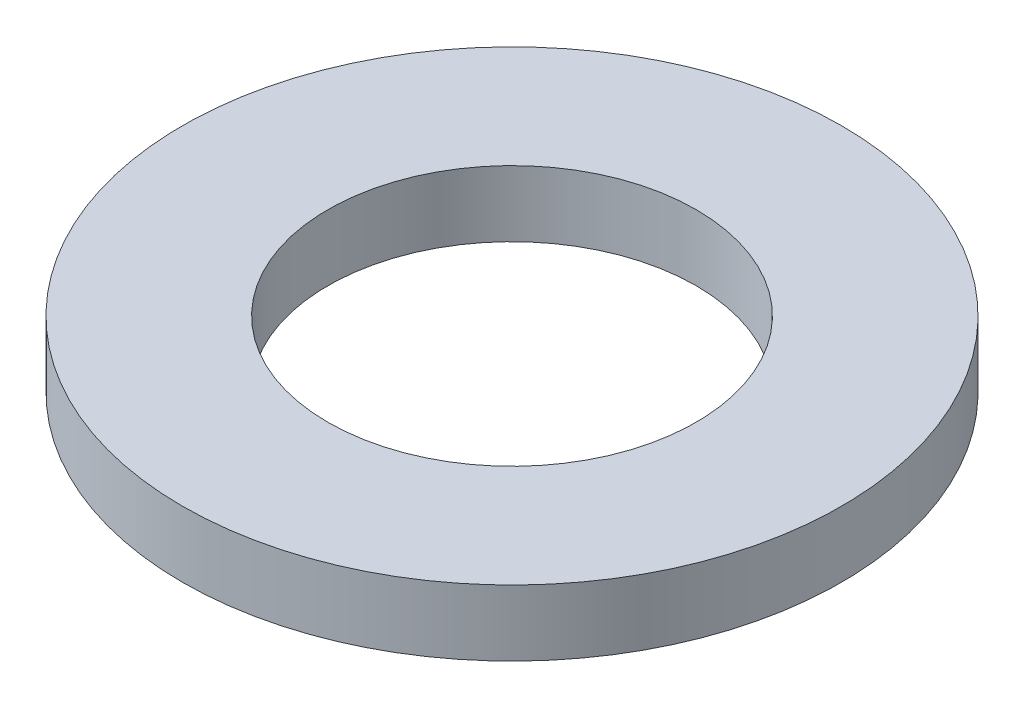
SolidWorks part; units mm, degrees
ref_plane "Front Plane" through (0, 0, 0) normal (0, 0, 1) x (1, 0, 0)
ref_plane "Top Plane" through (0, 0, 0) normal (0, 1, 0) x (1, 0, 0)
ref_plane "Right Plane" through (0, 0, 0) normal (1, 0, 0) x (0, 0, -1)
sketch "Sketch1" plane through (0, 0, 0) normal (0, 1, 0) x (1, 0, 0)
  circle A0 centre (0, 0) radius 85
  dimension "FLANGE_OD" = 170
extrude "Boss-Extrude1" add sketch "Sketch1" along normal blind 17
sketch "Sketch2" plane through (0, 0, 0) normal (0, 1, 0) x (1, 0, 0)
  circle A0 centre (0, 0) radius 47.5
  dimension "BORE_D" = 95
extrude "Cut-Extrude1" cut sketch "Sketch2" along normal through all
sketch "Sketch3" plane through (0, 17, 0) normal (0, 1, 0) x (1, 0, 0)
  circle A0 centre (0, 0) radius 30.7074 construction
  circle A1 centre (-30.7074, 0) radius 5.532
  dimension "BOLT_D" = 11.0639
  dimension "BOLT_PCD" = 61.4148
extrude "Cut-Extrude2" cut sketch "Sketch3" against normal blind 13.7502 rebuild error yes
pattern_circular "CirPattern1" count 3 over 360 rebuild error yes
